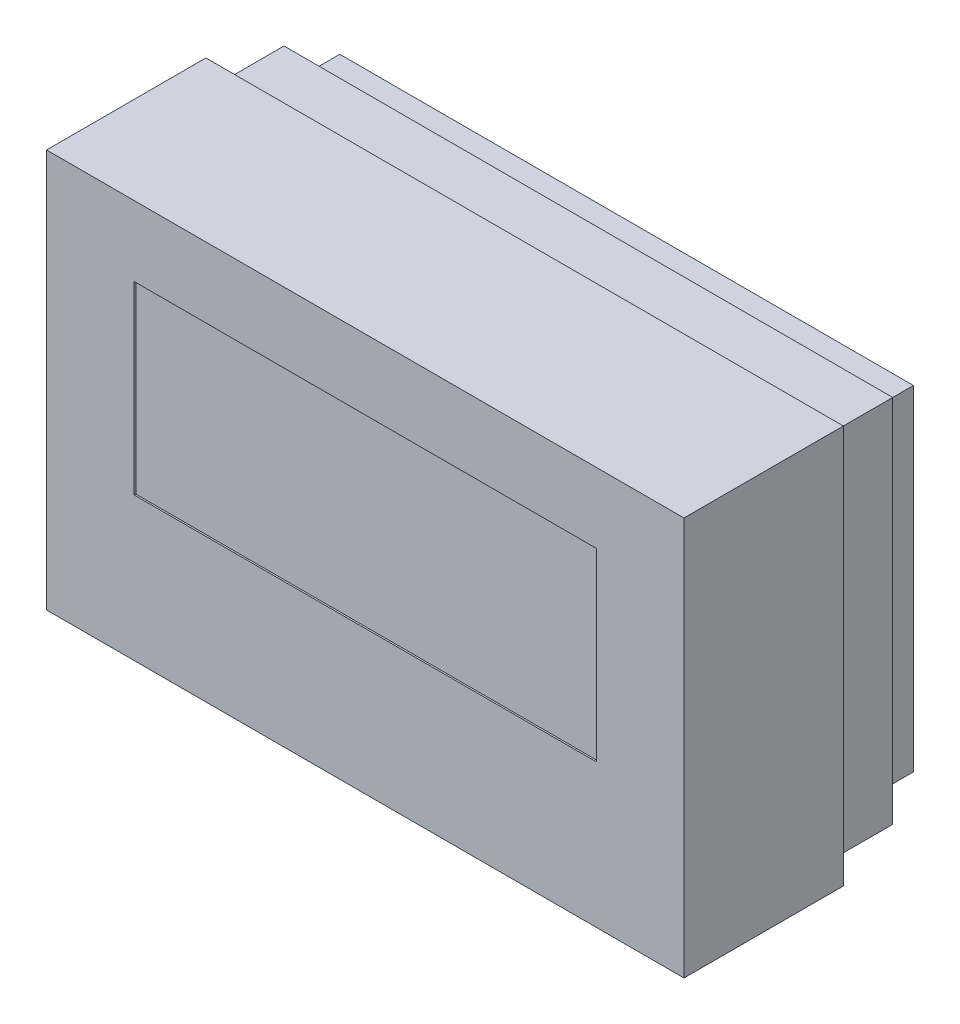
SolidWorks part; units mm, degrees
ref_plane "Front" through (0, 0, 0) normal (0, 0, 1) x (1, 0, 0)
ref_plane "Top" through (0, 0, 0) normal (0, 1, 0) x (1, 0, 0)
ref_plane "Right" through (0, 0, 0) normal (1, 0, 0) x (0, 0, -1)
sketch "Sketch1" plane through (0, 0, 0) normal (0, 0, 1) x (1, 0, 0)
  line L1 (-20, 12.5) -> (20, 12.5)
  line L2 (-20, 12.5) -> (-20, -12.5)
  line L3 (-20, -12.5) -> (20, -12.5)
  line L4 (20, 12.5) -> (20, -12.5)
  line L5 (-20, 12.5) -> (20, -12.5) construction
  line L6 (-20, -12.5) -> (20, 12.5) construction
  point P0 (0, 0)
  dimension "D1" = 40
  dimension "D2" = 25
extrude "Boss-Extrude1" add sketch "Sketch1" along normal blind 10
sketch "Sketch2" plane through (0, 0, 10) normal (0, 0, 1) x (1, 0, 0)
  line L0 (20, 12.5) -> (-20, 12.5) construction
  line L1 (-14.5, 8.1) -> (14.5, 8.1)
  line L2 (-14.5, 8.1) -> (-14.5, -3.5)
  line L3 (-14.5, -3.5) -> (14.5, -3.5)
  line L4 (14.5, 8.1) -> (14.5, -3.5)
  line L5 (-20, 12.5) -> (-20, -12.5) construction
  line L6 (20, -12.5) -> (20, 12.5) construction
  line L7 (-20, -12.5) -> (20, -12.5) construction
  dimension "D1" = 4.4
  dimension "D2" = 5.5
  dimension "D3" = 5.5
  dimension "D4" = 9
extrude "Cut-Extrude1" cut sketch "Sketch2" against normal blind 0.1 contours L2 L1 L4 L3
sketch "Sketch4" plane through (0, 0, 0) normal (0, 0, -1) x (-1, 0, 0)
  line L0 (-20, 12.5) -> (20, 12.5) construction
  line L1 (-19.1, 11.6) -> (19.1, 11.6)
  line L2 (-19.1, 11.6) -> (-19.1, -11.6)
  line L3 (-19.1, -11.6) -> (19.1, -11.6)
  line L4 (19.1, 11.6) -> (19.1, -11.6)
  line L5 (-19.1, 11.6) -> (19.1, -11.6) construction
  line L6 (-19.1, -11.6) -> (19.1, 11.6) construction
  line L7 (-20, -12.5) -> (-20, 12.5) construction
  point P0 (0, 0)
  dimension "D1" = 0.9
  dimension "D2" = 0.9
extrude "Boss-Extrude2" add sketch "Sketch4" along normal blind 4
sketch "Sketch5" plane through (0, 0, -4) normal (0, 0, -1) x (-1, 0, 0)
  line L0 (-20, 12.5) -> (20, 12.5) construction
  line L1 (-18, 10.5) -> (18, 10.5)
  line L2 (-18, 10.5) -> (-18, -10.5)
  line L3 (-18, -10.5) -> (18, -10.5)
  line L4 (18, 10.5) -> (18, -10.5)
  line L5 (-18, 10.5) -> (18, -10.5) construction
  line L6 (-18, -10.5) -> (18, 10.5) construction
  line L7 (-20, -12.5) -> (-20, 12.5) construction
  point P0 (0, 0)
  dimension "D1" = 2
  dimension "D2" = 2
extrude "Boss-Extrude3" add sketch "Sketch5" along normal blind 2.4
sketch "Sketch6" plane through (0, 0, -6.4) normal (0, 0, -1) x (-1, 0, 0)
  line L0 (20, -12.5) -> (-20, -12.5) construction
  line L1 (-19.1, 11.7) -> (21.3, 11.7)
  line L2 (-19.1, 11.7) -> (-19.1, -13.8)
  line L3 (-19.1, -13.8) -> (21.3, -13.8)
  line L4 (21.3, 11.7) -> (21.3, -13.8)
  line L5 (-20, 12.5) -> (20, 12.5) construction
  line L6 (20, 12.5) -> (20, -12.5) construction
  line L7 (-20, -12.5) -> (-20, 12.5) construction
  point P12 (-19.1, -1.05)
  dimension "D1" = 1.3
  dimension "D2" = 0.8
  dimension "D3" = 1.3
  dimension "D4" = 0.9
sketch "Sketch7" plane through (0, -11.6, 0) normal (0, -1, 0) x (1, 0, 0)
  line L0 (14.5, 0) -> (9.5, -5)
  line L1 (19.1, 0) -> (-19.1, 0) construction
  line L2 (9.5, -5) -> (-4.5, -5)
  line L3 (-4.5, -5) -> (-9.5, 0)
  line L4 (-9.5, 0) -> (14.5, 0)
  line L9 (20, 10) -> (20, 0) construction
  dimension "D1" = 45
  dimension "D2" = 24
  dimension "D3" = 14
  dimension "D4" = 5.5
extrude "Boss-Extrude5" add sketch "Sketch7" along normal blind 2.8 and the other way up to surface (1.1 mm away) other way up to face at (0, -10.5, -5.2)
fillet "Fillet1" radius 2 2 edges at (2.5, -14.4, 0) (2.5, -14.4, -5)
